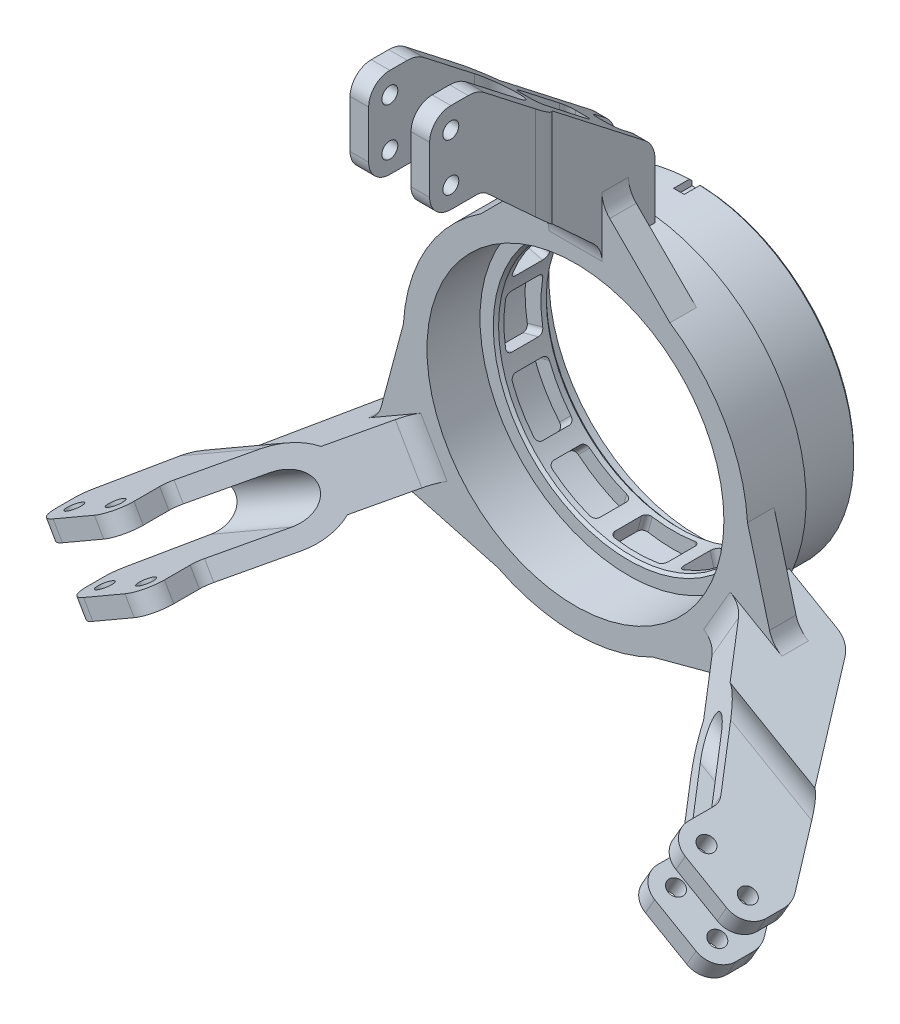
SolidWorks part; units mm, degrees
ref_plane "前视基准面" through (0, 0, 0) normal (0, 0, 1) x (1, 0, 0)
ref_plane "上视基准面" through (0, 0, 0) normal (0, 1, 0) x (1, 0, 0)
ref_plane "右视基准面" through (0, 0, 0) normal (1, 0, 0) x (0, 0, -1)
sketch "草图1" plane through (0, 0, 0) normal (1, 0, 0) x (0, 0, -1)
  line L0 (0, 22.5) -> (0, 0) construction
  line L1 (0, 0) -> (40.75, 0) construction
  line L5 (10, 28) -> (10, 25)
  line L6 (10, 25) -> (0, 25)
  line L7 (0, 25) -> (0, 28)
  line L12 (-10, 32.5) -> (13, 32.5)
  line L13 (10, 28) -> (13, 28)
  line L14 (13, 28) -> (13, 32.5)
  line L15 (0, 28) -> (-10, 28)
  line L16 (-10, 28) -> (-10, 32.5)
  dimension "D4" = 3
  dimension "D5" = 3
  dimension "D1" = 50
  dimension "D2" = 10
  dimension "D3" = 65
  dimension "D6" = 10
revolve "旋转1" add sketch "草图1" angle 360 about L1
sketch "草图2" plane through (0, 0, 10) normal (0, 0, 1) x (1, 0, 0)
  line L0 (0, 0) -> (0, 75) construction
  line L1 (-5, 75) -> (5, 75)
  line L2 (5, 75) -> (5, 40)
  line L3 (5, 40) -> (17.8229, 27.1771)
  line L4 (-5, 75) -> (-5, 40)
  line L5 (-5, 40) -> (-17.8229, 27.1771)
  circle A0 centre (0, 0) radius 32.5 construction
  arc A1 (17.8229, 27.1771) -> (-17.8229, 27.1771) centre (0, 0) ccw
  dimension "D1" = 10
  dimension "D2" = 90
  dimension "D3" = 75
  dimension "D4" = 40
extrude "凸台-拉伸1" add sketch "草图2" against normal blind 5
sketch "草图3" plane through (0, 0, 5) normal (0, 0, -1) x (-1, 0, 0)
  line L0 (5, 40) -> (5, 27.55)
  line L1 (-5, 40) -> (-5, 27.55)
  line L5 (-5, 75) -> (-5, 40)
  line L6 (-5, 40) -> (-17.8229, 27.1771)
  line L7 (17.8229, 27.1771) -> (5, 40)
  line L8 (5, 40) -> (5, 75)
  line L9 (5, 75) -> (-5, 75)
  line L10 (-5, 75) -> (-5, 40)
  line L13 (5, 40) -> (5, 75)
  line L14 (5, 75) -> (-5, 75)
  circle A0 centre (0, 0) radius 28 construction
  arc A1 (17.8229, 27.1771) -> (-17.8229, 27.1771) centre (0, 0) ccw
  arc A3 (5, 27.55) -> (-5, 27.55) centre (0, 0) ccw
  dimension "D1" = 0
extrude "凸台-拉伸2" add sketch "草图3" along normal blind 5 and the other way blind 45
sketch "草图4" plane through (0, 0, 0) normal (1, 0, 0) x (0, 0, -1)
  line L0 (0, 0) -> (-33.5601, 0) construction
  line L3 (-50, 27.55) -> (-10, 27.55) construction
  line L4 (-10, 27.55) -> (-50, 27.55)
  line L5 (-50, 27.55) -> (-50, 75)
  line L6 (0, 75) -> (-50, 75) construction
  line L7 (0, 75) -> (0, 45)
  line L8 (0, 75) -> (0, 32.1131) construction
  line L11 (0, 75) -> (-50, 75)
  line L13 (-10, 27.55) -> (-10, 33)
  line L14 (-10, 40) -> (-10, 27.55) construction
  line L17 (-36, 73) -> (0, 45)
  line L18 (-41, 56) -> (-35, 56)
  line L19 (-35, 56) -> (-10, 33)
  line L20 (-41, 60) -> (-41, 69) construction
  line L21 (-45, 69) -> (-45, 60)
  line L22 (-41, 73) -> (-36, 73)
  circle A0 centre (-41, 60) radius 1.5
  arc A1 (-45, 60) -> (-41, 56) centre (-41, 60) ccw
  circle A2 centre (-41, 69) radius 1.5
  arc A3 (-41, 73) -> (-45, 69) centre (-41, 69) ccw
  dimension "D1" = 3
  dimension "D2" = 8
  dimension "D3" = 41
  dimension "D4" = 120
  dimension "D10" = 5
  dimension "D5" = 33
  dimension "D6" = 6
  dimension "D7" = 45
  dimension "D9" = 9
extrude "切除-拉伸1" cut sketch "草图4" against normal mid plane 20
pattern_circular "阵列(圆周)1" count 3 over 360 about axis through (0, 0, 0) along (0, 0, 1) of "凸台-拉伸1", "切除-拉伸1", "凸台-拉伸2"
sketch "草图5" plane through (0, 0, 0) normal (1, 0, 0) x (0, 0, -1)
  line L0 (-10, 33) -> (-10, 52.7778)
  line L1 (-36, 73) -> (0, 45) construction
  line L2 (-10, 52.7778) -> (-36, 73)
  line L4 (-10, 33) -> (-35, 56) construction
  line L5 (-35, 56) -> (-41, 56) construction
  line L6 (-10, 33) -> (-35, 56)
  line L7 (-35, 56) -> (-41, 56)
  line L8 (-45, 60) -> (-45, 69) construction
  line L9 (-41, 73) -> (-36, 73) construction
  line L10 (-45, 60) -> (-45, 69)
  line L11 (-41, 73) -> (-36, 73)
  arc A0 (-45, 60) -> (-41, 56) centre (-41, 60) ccw construction
  arc A1 (-45, 60) -> (-41, 56) centre (-41, 60) ccw
  circle A2 centre (-41, 60) radius 1.5 construction
  circle A3 centre (-41, 60) radius 1.5
  circle A4 centre (-41, 69) radius 1.5 construction
  arc A5 (-41, 73) -> (-45, 69) centre (-41, 69) ccw construction
  circle A6 centre (-41, 69) radius 1.5
  arc A7 (-41, 73) -> (-45, 69) centre (-41, 69) ccw
extrude "凸台-拉伸3" add sketch "草图5" along normal mid plane 15
sketch "草图6" plane through (0, 0, 0) normal (0, 1, 0) x (1, 0, 0)
  line L0 (0, 0) -> (0, -77.9712) construction
  line L1 (-4, -45) -> (4, -45)
  line L3 (4, -25) -> (4, -45)
  line L4 (-4, -25) -> (-4, -45)
  line L5 (5, -10) -> (5, -19.4098)
  line L6 (-14.6246, -10) -> (14.6246, -10) construction
  line L7 (5, -10) -> (7.5, -10)
  line L8 (7.5, -10) -> (7.5, -25)
  line L9 (-5, -10) -> (-7.5, -10)
  line L10 (-7.5, -10) -> (-7.5, -25)
  line L11 (-5, -10) -> (-5, -19.4098)
  line L12 (7.5, -10) -> (7.5, -36) construction
  line L13 (-7.5, -45) -> (7.5, -45) construction
  arc A0 (4, -25) -> (-4, -25) centre (0, -25) ccw
  arc A1 (7.5, -25) -> (5, -19.4098) centre (0, -25) ccw
  arc A2 (-7.5, -25) -> (-5, -19.4098) centre (0, -25) cw
  dimension "D1" = 8
  dimension "D3" = 10
  dimension "D2" = 20
extrude "切除-拉伸2" cut sketch "草图6" along normal through all
pattern_circular "阵列(圆周)2" count 3 over 360 about axis through (0, 0, 0) along (0, 0, 1) of "切除-拉伸2", "凸台-拉伸3"
fillet "圆角1" radius 3 6 edges at (-51.3724, -23.0204, 35) (-45.6224, -32.9796, 35) (45.6224, -32.9796, 35) (51.3724, -23.0204, 35) (-5.75, 56, 35) (5.75, 56, 35)
fillet "圆角2" radius 5 18 edges at (32.141, -24.3301, 7.5) (37.141, -15.6699, 7.5) (-37.141, -15.6699, 7.5) (-32.141, -24.3301, 7.5) (5, 40, 7.5) (-5, 40, 7.5) (-38.9711, -22.5, 0) (38.9711, -22.5, 0) (66.0949, -31.5204, 36) (-60.3449, -41.4796, 36) (5.75, 73, 36) (0, 33, 10) (0, 45, 0) (60.3449, -41.4796, 36) (28.5788, -16.5, 10) (-66.0949, -31.5204, 36) (-28.5788, -16.5, 10) (-5.75, 73, 36)
sketch "草图7" plane through (0, 0, 0) normal (1, 0, 0) x (0, 0, -1)
  line L0 (-19.4098, 60.0965) -> (-19.4098, 47.0923)
  line L1 (-19.4098, 47.0923) -> (-9, 37.5153)
  line L2 (-9, 37.5153) -> (-9, 52)
  line L3 (-19.4098, 60.0965) -> (-1.9303, 46.5013) construction
  line L4 (-9, 52) -> (-19.4098, 60.0965)
  line L5 (0, 33) -> (-5, 33)
  line L6 (0, 42.5546) -> (0, 32.1131) construction
  line L7 (-5, 33) -> (-5, 48.8889)
  line L8 (-5, 48.8889) -> (-1.9303, 46.5013)
  line L9 (0, 33) -> (0, 42.5546)
  line L10 (-19.4098, 41.657) -> (-11.6147, 34.4855) construction
  arc A0 (0, 42.5546) -> (-1.9303, 46.5013) centre (-5, 42.5546) ccw construction
  arc A1 (0, 42.5546) -> (-1.9303, 46.5013) centre (-5, 42.5546) ccw
  dimension "D1" = 4
  dimension "D2" = 33
  dimension "D3" = 5
  dimension "D4" = 4
extrude "切除-拉伸3" cut sketch "草图7" against normal mid plane 5
sketch "草图8" plane through (0, 0, 0) normal (0, 0, -1) x (-1, 0, 0)
  line L0 (2.5, 33) -> (-2.5, 33) construction
  line L1 (2.5, 33) -> (-2.5, 33)
  line L2 (-2.5, 33) -> (-2.5, 32.4037)
  line L3 (2.5, 33) -> (2.5, 32.4037)
  arc A0 (5, 32.1131) -> (-5, 32.1131) centre (0, 0) ccw construction
  arc A1 (2.5, 32.4037) -> (-2.5, 32.4037) centre (0, 0) ccw
extrude "切除-拉伸4" cut sketch "草图8" against normal up to surface (5 mm away) up to face at (0, 40.9444, 5)
fillet "圆角3" radius 1.5 6 edges at (-2.5, 53.5944, 19.4098) (2.5, 44.7576, 9) (-2.5, 44.7576, 9) (2.5, 53.5944, 19.4098) (2.5, 40.6463, 5) (-2.5, 40.6463, 5)
pattern_circular "阵列(圆周)3" count 3 over 360 about axis through (0, 0, 0) along (0, 0, 1) of "切除-拉伸3", "切除-拉伸4", "圆角3"
sketch "草图9" plane through (0, 0, -13) normal (0, 0, -1) x (-1, 0, 0)
  circle A0 centre (0, 0) radius 30
  circle A1 centre (0, 0) radius 32.5 construction
  circle A2 centre (0, 0) radius 32.5
  dimension "D1" = 60
extrude "切除-拉伸5" cut sketch "草图9" against normal blind 12
chamfer "倒角1" distance 0.5 angle 45 1 edges at (-30, 0, -13)
ref_plane "基准面2" through (0, 0, -1.5) normal (0, 0, 1) x (1, 0, 0)
sketch "草图11" plane through (0, 0, -1.5) normal (0, 0, 1) x (1, 0, 0)
  line L0 (0, 0) -> (0, 28) construction
  line L1 (0, 0) -> (7.2469, 27.0459) construction
  line L2 (5.0099, 24.4929) -> (5.7876, 27.3953)
  line L3 (-5.0099, 24.4929) -> (-5.7876, 27.3953)
  line L4 (0, 0) -> (-7.2469, 27.0459) construction
  line L5 (16.5852, 18.7065) -> (18.7099, 20.8312)
  line L6 (7.9077, 23.7164) -> (8.6854, 26.6189)
  line L7 (23.7164, 7.9077) -> (26.6189, 8.6854)
  line L8 (18.7065, 16.5852) -> (20.8312, 18.7099)
  line L9 (24.4929, -5.0099) -> (27.3953, -5.7876)
  line L10 (24.4929, 5.0099) -> (27.3953, 5.7876)
  line L11 (18.7065, -16.5852) -> (20.8312, -18.7099)
  line L12 (23.7164, -7.9077) -> (26.6189, -8.6854)
  line L13 (7.9077, -23.7164) -> (8.6854, -26.6189)
  line L14 (16.5852, -18.7065) -> (18.7099, -20.8312)
  line L15 (-5.0099, -24.4929) -> (-5.7876, -27.3953)
  line L16 (5.0099, -24.4929) -> (5.7876, -27.3953)
  line L17 (-16.5852, -18.7065) -> (-18.7099, -20.8312)
  line L18 (-7.9077, -23.7164) -> (-8.6854, -26.6189)
  line L19 (-23.7164, -7.9077) -> (-26.6189, -8.6854)
  line L20 (-18.7065, -16.5852) -> (-20.8312, -18.7099)
  line L21 (-24.4929, 5.0099) -> (-27.3953, 5.7876)
  line L22 (-24.4929, -5.0099) -> (-27.3953, -5.7876)
  line L23 (-18.7065, 16.5852) -> (-20.8312, 18.7099)
  line L24 (-23.7164, 7.9077) -> (-26.6189, 8.6854)
  line L25 (-7.9077, 23.7164) -> (-8.6854, 26.6189)
  line L26 (-16.5852, 18.7065) -> (-18.7099, 20.8312)
  circle A0 centre (0, 0) radius 28 construction
  circle A1 centre (0, 0) radius 25 construction
  circle A2 centre (0, 0) radius 28
  arc A3 (5.7876, 27.3953) -> (-5.7876, 27.3953) centre (0, 0) ccw
  arc A4 (5.0099, 24.4929) -> (-5.0099, 24.4929) centre (0, 0) ccw
  circle A5 centre (0, 0) radius 28 construction
  arc A6 (18.7099, 20.8312) -> (8.6854, 26.6189) centre (0, 0) ccw
  arc A7 (16.5852, 18.7065) -> (7.9077, 23.7164) centre (0, 0) ccw
  arc A8 (26.6189, 8.6854) -> (20.8312, 18.7099) centre (0, 0) ccw
  arc A9 (23.7164, 7.9077) -> (18.7065, 16.5852) centre (0, 0) ccw
  arc A10 (27.3953, -5.7876) -> (27.3953, 5.7876) centre (0, 0) ccw
  arc A11 (24.4929, -5.0099) -> (24.4929, 5.0099) centre (0, 0) ccw
  arc A12 (20.8312, -18.7099) -> (26.6189, -8.6854) centre (0, 0) ccw
  arc A13 (18.7065, -16.5852) -> (23.7164, -7.9077) centre (0, 0) ccw
  arc A14 (8.6854, -26.6189) -> (18.7099, -20.8312) centre (0, 0) ccw
  arc A15 (7.9077, -23.7164) -> (16.5852, -18.7065) centre (0, 0) ccw
  arc A16 (-5.7876, -27.3953) -> (5.7876, -27.3953) centre (0, 0) ccw
  arc A17 (-5.0099, -24.4929) -> (5.0099, -24.4929) centre (0, 0) ccw
  arc A18 (-18.7099, -20.8312) -> (-8.6854, -26.6189) centre (0, 0) ccw
  arc A19 (-16.5852, -18.7065) -> (-7.9077, -23.7164) centre (0, 0) ccw
  arc A20 (-26.6189, -8.6854) -> (-20.8312, -18.7099) centre (0, 0) ccw
  arc A21 (-23.7164, -7.9077) -> (-18.7065, -16.5852) centre (0, 0) ccw
  arc A22 (-27.3953, 5.7876) -> (-27.3953, -5.7876) centre (0, 0) ccw
  arc A23 (-24.4929, 5.0099) -> (-24.4929, -5.0099) centre (0, 0) ccw
  arc A24 (-20.8312, 18.7099) -> (-26.6189, 8.6854) centre (0, 0) ccw
  arc A25 (-18.7065, 16.5852) -> (-23.7164, 7.9077) centre (0, 0) ccw
  arc A26 (-8.6854, 26.6189) -> (-18.7099, 20.8312) centre (0, 0) ccw
  arc A27 (-7.9077, 23.7164) -> (-16.5852, 18.7065) centre (0, 0) ccw
  point P64 (0, 0)
  dimension "D1" = 0
  dimension "D2" = 3
  dimension "D3" = 30
  dimension "D4" = 12
extrude "切除-拉伸6" cut sketch "草图11" against normal blind 7
fillet "圆角4" radius 1 48 edges at (-17.6475, -19.7689, -8.5) (-17.6475, -19.7689, -1.5) (-8.2966, -25.1676, -1.5) (-8.2966, -25.1676, -8.5) (-5.3988, -25.9441, -8.5) (-5.3988, -25.9441, -1.5) (5.3988, -25.9441, -1.5) (5.3988, -25.9441, -8.5) (19.7689, -17.6475, -8.5) (19.7689, -17.6475, -1.5) (25.1676, -8.2966, -1.5) (25.1676, -8.2966, -8.5) (25.1676, 8.2966, -8.5) (25.1676, 8.2966, -1.5) (19.7689, 17.6475, -1.5) (19.7689, 17.6475, -8.5) (-8.2966, 25.1676, -8.5) (-8.2966, 25.1676, -1.5) (-17.6475, 19.7689, -1.5) (-17.6475, 19.7689, -8.5) (-25.9441, 5.3988, -8.5) (-25.9441, 5.3988, -1.5) (-25.9441, -5.3988, -1.5) (-25.9441, -5.3988, -8.5) (17.6475, 19.7689, -8.5) (17.6475, 19.7689, -1.5) (8.2966, 25.1676, -1.5) (8.2966, 25.1676, -8.5) (-19.7689, 17.6475, -8.5) (-25.1676, 8.2966, -8.5) (5.3988, 25.9441, -8.5) (5.3988, 25.9441, -1.5) (-5.3988, 25.9441, -1.5) (-5.3988, 25.9441, -8.5) (25.9441, -5.3988, -8.5) (25.9441, -5.3988, -1.5) (25.9441, 5.3988, -1.5) (25.9441, 5.3988, -8.5) (8.2966, -25.1676, -8.5) (8.2966, -25.1676, -1.5) (17.6475, -19.7689, -1.5) (17.6475, -19.7689, -8.5) (-25.1676, -8.2966, -8.5) (-25.1676, -8.2966, -1.5) (-19.7689, -17.6475, -1.5) (-19.7689, -17.6475, -8.5) (-25.1676, 8.2966, -1.5) (-19.7689, 17.6475, -1.5)
chamfer "倒角2" distance 0.5 angle 45 2 edges at (25, 0, 0) (25, 0, -10)
sketch "草图12" plane through (0, 0, -13) normal (0, 0, -1) x (-1, 0, 0)
  line L0 (0, 0) -> (0, 30.7736) construction
  line L2 (-1, 32.889) -> (1, 32.889)
  line L3 (-1, 32.889) -> (-1, 28.6583)
  line L4 (-1, 28.6583) -> (1, 28.6583)
  line L5 (1, 32.889) -> (1, 28.6583)
  line L6 (-1, 32.889) -> (1, 28.6583) construction
  line L7 (-1, 28.6583) -> (1, 32.889) construction
  dimension "D1" = 2
extrude "切除-拉伸7" cut sketch "草图12" against normal blind 3.5
